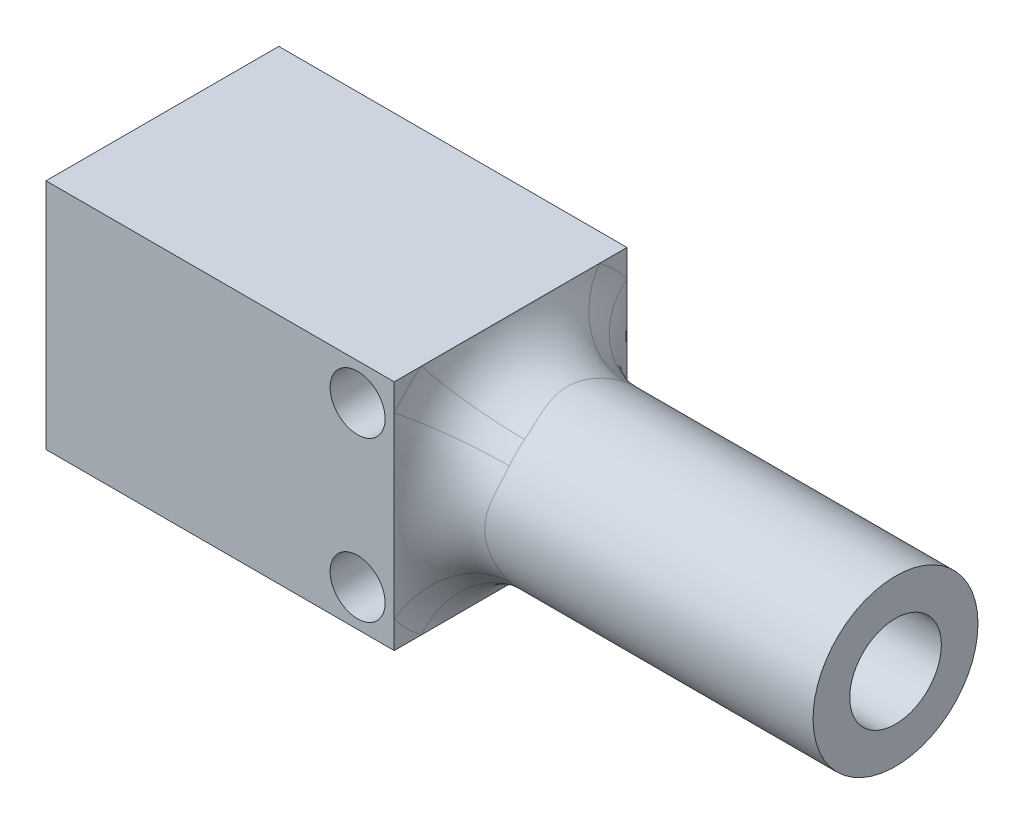
SolidWorks part; units mm, degrees
ref_plane "Ebene vorne" through (0, 0, 0) normal (1, 0, 0) x (0, 1, 0)
ref_plane "Ebene oben" through (0, 0, 0) normal (0, 0, 1) x (0, 1, 0)
ref_plane "Ebene rechts" through (0, 0, 0) normal (0, 1, 0) x (-1, 0, 0)
sketch "Skizze5" plane through (0, 0, 0) normal (1, 0, 0) x (0, 1, 0)
  line L1 (-12.7, -12.7) -> (12.7, -12.7)
  line L2 (-12.7, -12.7) -> (-12.7, 12.7)
  line L3 (-12.7, 12.7) -> (12.7, 12.7)
  line L4 (12.7, -12.7) -> (12.7, 12.7)
  line L5 (-12.7, -12.7) -> (12.7, 12.7) construction
  line L6 (-12.7, 12.7) -> (12.7, -12.7) construction
  point P0 (0, 0)
  dimension "D1" = 25.4
  dimension "D2" = 25.4
extrude "Motorarm" add sketch "Skizze5" along normal blind 60 and the other way blind 20
sketch "Skizze6" plane through (60, 0, 0) normal (1, 0, 0) x (0, 1, 0)
  circle A0 centre (0, 0) radius 5
  dimension "D1" = 10
extrude "Welle" cut sketch "Skizze6" against normal blind 100
sketch "Skizze7" plane through (-20, 0, 0) normal (-1, 0, 0) x (0, -1, 0)
  line L5 (-8.5, -8.5) -> (8.5, 8.5) construction
  line L6 (-8.5, 8.5) -> (8.5, -8.5) construction
  circle A0 centre (-8.5, 8.5) radius 2
  circle A1 centre (8.5, 8.5) radius 2
  circle A2 centre (-8.5, -8.5) radius 2
  circle A3 centre (8.5, -8.5) radius 2
  point P0 (0, 0)
  dimension "D1" = 17
  dimension "D2" = 17
extrude "Löcher AS5600" cut sketch "Skizze7" against normal blind 7
sketch "Skizze9" plane through (0, 0, -12.7) normal (0, 0, -1) x (1, 0, 0)
  line L8 (0, 9.5) -> (-8.2272, 4.75) construction
  line L9 (-8.2272, 4.75) -> (-8.2272, -4.75) construction
  line L10 (-8.2272, -4.75) -> (0, -9.5) construction
  line L11 (0, -9.5) -> (8.2272, -4.75) construction
  line L12 (8.2272, -4.75) -> (8.2272, 4.75) construction
  line L13 (8.2272, 4.75) -> (0, 9.5) construction
  circle A4 centre (0, 0) radius 8.2272 construction
  circle A5 centre (0, 9.5) radius 2
  circle A6 centre (8.2272, 4.75) radius 2
  circle A7 centre (8.2272, -4.75) radius 2
  circle A8 centre (0, -9.5) radius 2
  circle A9 centre (-8.2272, -4.75) radius 2
  circle A10 centre (-8.2272, 4.75) radius 2
  circle A11 centre (0, 0) radius 12.7 construction
extrude "Löcher Motoraufnahme" cut sketch "Skizze9" against normal blind 7
sketch "Skizze10" plane through (0, 0, 0) normal (1, 0, 0) x (0, 1, 0)
  circle A0 centre (0, 0) radius 6.5
  dimension "D1" = 13
extrude "Kugellager 1" cut sketch "Skizze10" along normal blind 5 from offset 12
sketch "Skizze11" plane through (0, 0, 0) normal (1, 0, 0) x (0, 1, 0)
  circle A0 centre (0, 0) radius 6.5
  dimension "D1" = 13
extrude "Kugellager 2" cut sketch "Skizze11" along normal blind 5 from offset 40
sketch "Skizze12" plane through (0, 0, 0) normal (1, 0, 0) x (0, 1, 0)
  circle A1 centre (0, 0) radius 9
  dimension "D1" = 18
extrude "Materialreduzierung" cut sketch "Skizze12" along normal blind 42 from offset 18 flip side to cut
fillet "Übergang" radius 7 1 edges at (18, 0, -9)
sketch "Skizze14" plane through (0, 0, -12.7) normal (0, 0, -1) x (1, 0, 0)
  line L15 (18, 12.7) -> (14, 12.7) construction
  line L16 (18, 12.7) -> (18, 8.7) construction
  line L17 (18, 8.7) -> (14, 8.7) construction
  line L18 (14, 12.7) -> (14, 8.7) construction
  line L19 (17.3, 8.7) -> (15.65, 11.5579)
  line L20 (15.65, 11.5579) -> (12.35, 11.5579)
  line L21 (12.35, 11.5579) -> (10.7, 8.7)
  line L22 (10.7, 8.7) -> (12.35, 5.8421)
  line L23 (12.35, 5.8421) -> (15.65, 5.8421)
  line L24 (15.65, 5.8421) -> (17.3, 8.7)
  line L25 (18, -12.7) -> (14, -12.7) construction
  line L26 (18, -12.7) -> (18, -8.7) construction
  line L27 (18, -8.7) -> (14, -8.7) construction
  line L28 (14, -12.7) -> (14, -8.7) construction
  line L29 (17.3, -8.7) -> (15.65, -5.8421)
  line L30 (15.65, -5.8421) -> (12.35, -5.8421)
  line L31 (12.35, -5.8421) -> (10.7, -8.7)
  line L32 (10.7, -8.7) -> (12.35, -11.5579)
  line L33 (12.35, -11.5579) -> (15.65, -11.5579)
  line L34 (15.65, -11.5579) -> (17.3, -8.7)
  circle A0 centre (14, 8.7) radius 3.3 construction
  circle A1 centre (14, 8.7) radius 2.8579 construction
  circle A2 centre (14, -8.7) radius 3.3 construction
  circle A3 centre (14, -8.7) radius 2.8579 construction
  dimension "D3" = 4
  dimension "D1" = 4
  dimension "D2" = 4
  dimension "D4" = 4
extrude "Platz für Muttern" cut sketch "Skizze14" against normal blind 3
sketch "Skizze17" plane through (0, 0, -12.7) normal (0, 0, -1) x (1, 0, 0)
  circle A0 centre (14, -8.7) radius 3.3 construction
  circle A1 centre (14, -8.7) radius 1.6
  circle A2 centre (14, 8.7) radius 3.3 construction
  circle A3 centre (14, 8.7) radius 1.6
  dimension "D1" = 3.2
extrude "Platz für Stange" cut sketch "Skizze17" against normal blind 25.4
sketch "Skizze18" plane through (0, 0, 12.7) normal (0, 0, 1) x (1, 0, 0)
  circle A0 centre (14, 8.7) radius 3
  circle A1 centre (14, -8.7) radius 3
  dimension "D1" = 6
extrude "Platz für Schraubenkopf" cut sketch "Skizze18" against normal blind 6
